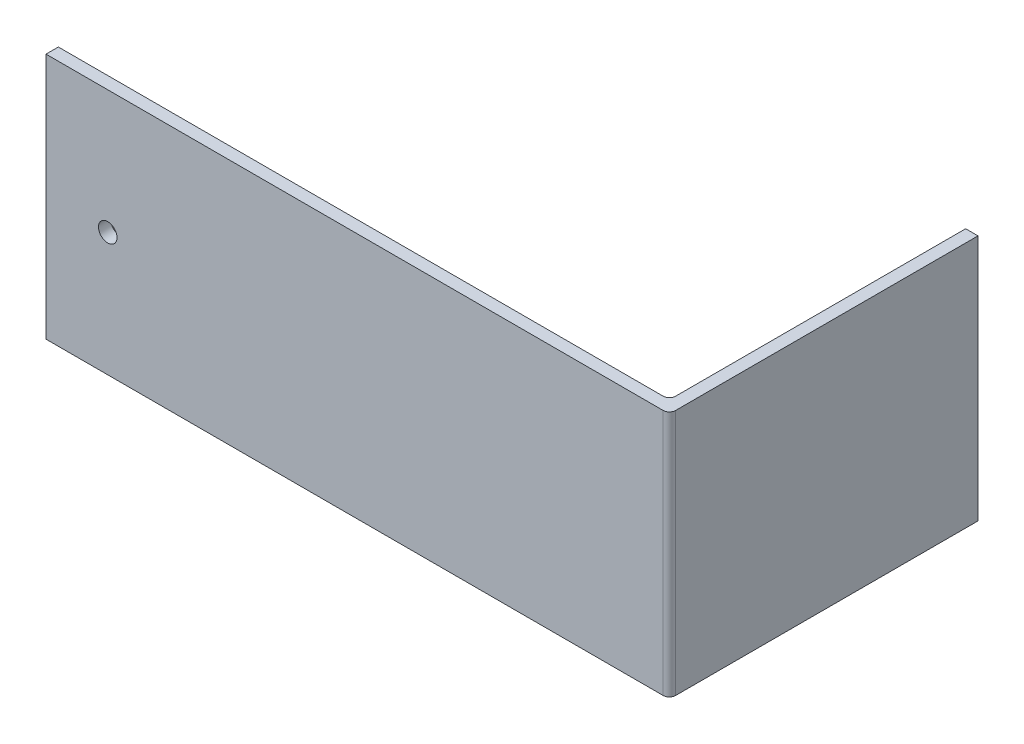
SolidWorks part; units mm, degrees
ref_plane "Front Plane" through (0, 0, 0) normal (0, 0, 1) x (1, 0, 0)
ref_plane "Top Plane" through (0, 0, 0) normal (0, 1, 0) x (1, 0, 0)
ref_plane "Right Plane" through (0, 0, 0) normal (1, 0, 0) x (0, 0, -1)
sketch "Sketch1" plane through (0, 0, 0) normal (0, 0, 1) x (1, 0, 0)
  line L1 (0, 0) -> (100, 0)
  line L2 (0, 0) -> (0, 40)
  line L3 (0, 40) -> (100, 40)
  line L4 (100, 0) -> (100, 40)
  circle A0 centre (10, 20) radius 1.5
  dimension "D3" = 20
  dimension "D4" = 10
  dimension "D1" = 40
  dimension "D2" = 100
extrude "Boss-Extrude1" add sketch "Sketch1" along normal blind 2
sketch "Sketch2" plane through (0, 0, 2) normal (0, 0, 1) x (1, 0, 0)
  line L0 (0, 0) -> (100, 0) construction
  line L1 (100, 40) -> (101, 40)
  line L2 (100, 40) -> (100, 0)
  line L3 (100, 0) -> (101, 0)
  line L4 (101, 40) -> (101, 0)
  line L5 (100, 40) -> (99, 40)
  line L6 (100, 40) -> (100, 0)
  line L7 (100, 0) -> (99, 0)
  line L8 (99, 40) -> (99, 0)
  line M2 (0, 0) -> (100, 0)
  line M3 (100, 0) -> (100, 40)
  line M4 (100, 40) -> (0, 40)
  dimension "D1" = 1
  dimension "D2" = 1
extrude "Boss-Extrude3" add sketch "Sketch2" against normal blind 50 contours L4 L1 L3 M3 | L8 M4 M2 M3 region at (100.5, 20, 2) region at (99.5, 20, 2)
fillet "Fillet2" radius 1 2 edges at (101, 20, 2) (99, 20, 0)
